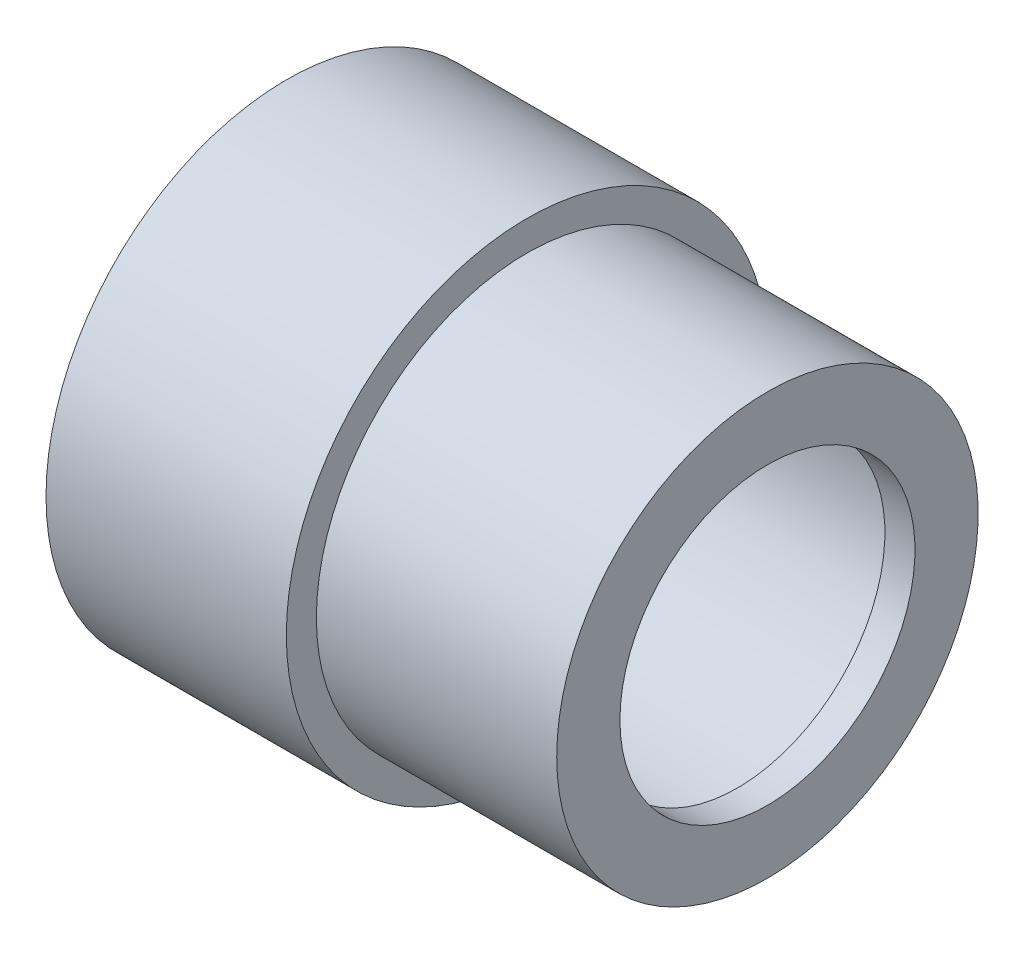
SolidWorks part; units mm, degrees
ref_plane "Front Plane" through (0, 0, 0) normal (0, 0, 1) x (1, 0, 0)
ref_plane "Top Plane" through (0, 0, 0) normal (0, 1, 0) x (1, 0, 0)
ref_plane "Right Plane" through (0, 0, 0) normal (1, 0, 0) x (0, 0, -1)
sketch "Sketch1" plane through (0, 0, 0) normal (0, 0, 1) x (1, 0, 0)
  line L0 (0, 0) -> (0, 76.2) construction
  line L1 (0, 0) -> (248.6575, 0) construction
  line L2 (0, 89.0805) -> (0, 101.7805)
  line L3 (0, 101.7805) -> (101.6, 101.7805)
  line L4 (101.6, 101.7805) -> (101.6, 89.0805)
  line L5 (101.6, 89.0805) -> (203.2, 89.0805)
  line L6 (203.2, 89.0805) -> (203.2, 62.3614)
  line L7 (0, 89.0805) -> (88.9, 89.0805)
  line L8 (88.9, 89.0805) -> (88.9, 76.3805)
  line L9 (88.9, 76.3805) -> (190.5, 76.3805)
  line L10 (190.5, 76.3805) -> (190.5, 62.3614)
  line L11 (190.5, 62.3614) -> (203.2, 62.3614)
  line L12 (88.9, 89.0805) -> (101.6, 89.0805) construction
  dimension "D1" = 76.2
  dimension "D2" = 88.9
  dimension "D3" = 12.7
  dimension "D4" = 101.6
revolve "Revolve1" add sketch "Sketch1" angle 360 about L1
sketch "Sketch7" plane through (0, 0, 0) normal (-1, 0, 0) x (0, 0, 1)
  circle A0 centre (0, 0) radius 101.7805
curve "Helix/Spiral1" pitch 11.43 height 45.72 turns 4
sketch "Sketch11" plane through (0, 0, 0) normal (0, 0, 1) x (1, 0, 0)
  line L0 (0, 0) -> (0, 101.7805) construction
  line L1 (101.6, 101.7805) -> (0, 101.7805) construction
  line L2 (0, 101.7805) -> (0, -101.7805) construction
